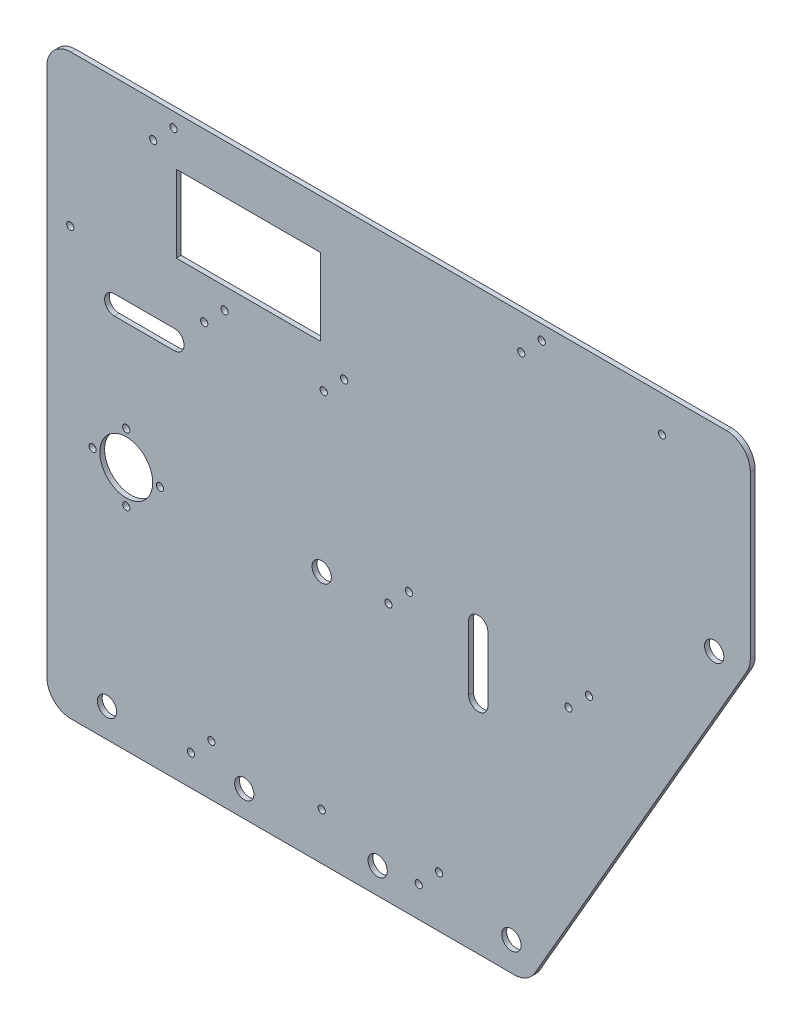
SolidWorks part; units mm, degrees
ref_plane "Front Plane" through (0, 0, 0) normal (0, 0, 1) x (1, 0, 0)
ref_plane "Top Plane" through (0, 0, 0) normal (0, 1, 0) x (1, 0, 0)
ref_plane "Right Plane" through (0, 0, 0) normal (1, 0, 0) x (0, 0, -1)
sketch "Sketch1" plane through (0, 0, 0) normal (0, 0, 1) x (1, 0, 0)
  line L0 (100, 80) -> (192.376, 80)
  line L1 (-100, -80) -> (100, -80)
  line L2 (-100, -80) -> (-100, 80)
  line L3 (-100, 80) -> (100, 80)
  line L4 (100, -80) -> (100, 80)
  line L5 (-100, -80) -> (100, 80) construction
  line L6 (-100, 80) -> (100, -80) construction
  line L7 (192.376, 80) -> (100, -80)
  line L8 (100, 80) -> (100, -80)
  line L10 (-100, 80) -> (192.376, 80)
  line L11 (-100, 80) -> (-100, 110)
  line L12 (-100, 110) -> (192.376, 110)
  line L13 (192.376, 80) -> (192.376, 110)
  point P0 (0, 0)
  dimension "D1" = 160
  dimension "D2" = 200
  dimension "D3" = 30
  dimension "D4" = 30
extrude "Boss-Extrude1" add sketch "Sketch1" along normal blind 2 contours L1 L4 L3 L2 | L7 L0 L4 | L11 L10 L13 L12 region at (0, 0, 0) region at (130.792, 26.6667, 0)
sketch "Sketch2" plane through (0, 0, 2) normal (0, 0, 1) x (1, 0, 0)
  line L0 (-100, -80) -> (100, -80) construction
  line L1 (192.376, 80) -> (100, -80) construction
  line L2 (79.2904, 11.2418) -> (79.2904, 37.9086) construction
  line L3 (-100, -80) -> (-100, 110) construction
  line L4 (-72, 78) -> (-47, 78) construction
  line L7 (-100, 110) -> (192.376, 110) construction
  line L8 (75.2904, 11.2418) -> (75.2904, 37.9086)
  line L9 (-72, 82) -> (-47, 82)
  line L10 (-72, 74) -> (-47, 74)
  line L11 (-100, -80) -> (-100, 110) construction
  line L12 (83.2904, 11.2418) -> (83.2904, 37.9086)
  circle A0 centre (93.0718, -68) radius 4
  circle A1 centre (177.3649, 78) radius 4
  circle A2 centre (-67, 22) radius 11
  circle A3 centre (-75, -68) radius 4
  circle A4 centre (-53, 22) radius 1.5
  circle A5 centre (-67, 36) radius 1.5
  circle A6 centre (-81, 22) radius 1.5
  circle A7 centre (-67, 8) radius 1.5
  circle A11 centre (54.5495, -67.2426) radius 1.5
  circle A12 centre (63.0348, -58.7574) radius 1.5
  circle A13 centre (14.2259, -60.5) radius 1.5
  circle A14 centre (-40.1271, -67.2426) radius 1.5
  circle A15 centre (-31.6419, -58.7574) radius 1.5
  circle A16 centre (-90.2956, 97.2169) radius 1.5
  circle A17 centre (-34.6051, 90.4743) radius 1.5
  circle A18 centre (-26.1198, 98.9596) radius 1.5
  circle A19 centre (15.0782, 90.4743) radius 1.5
  circle A20 centre (23.5635, 98.9596) radius 1.5
  circle A21 centre (41.9695, 27.4743) radius 1.5
  circle A22 centre (50.4548, 35.9596) radius 1.5
  circle A23 centre (-39.813, 27.4743) radius 1.5 construction
  circle A24 centre (-31.3277, 35.9596) radius 1.5 construction
  circle A25 centre (116.8113, 27.4743) radius 1.5
  circle A26 centre (125.2966, 35.9596) radius 1.5
  circle A27 centre (79.2904, 25) radius 4 construction
  circle A28 centre (14.2259, 25) radius 4
  arc A29 (-72, 82) -> (-72, 74) centre (-72, 78) ccw
  arc A30 (-47, 74) -> (-47, 82) centre (-47, 78) ccw
  circle A31 centre (155.6518, 145.1456) radius 1.5
  arc A32 (75.2904, 11.2418) -> (83.2904, 11.2418) centre (79.2904, 11.2418) ccw
  arc A33 (83.2904, 37.9086) -> (75.2904, 37.9086) centre (79.2904, 37.9086) ccw
  circle A34 centre (-55.8147, 145.4743) radius 1.5
  circle A35 centre (-47.3294, 153.9596) radius 1.5
  circle A36 centre (97.1924, 145.4743) radius 1.5
  circle A37 centre (105.6777, 153.9596) radius 1.5
  circle A38 centre (-17.9479, -69.1174) radius 4
  circle A39 centre (37.4944, -69.1174) radius 4
  point P26 (-59.5, 78)
  point P87 (79.2904, 24.5752)
  dimension "D3" = 8
  dimension "D4" = 8
  dimension "D9" = 22
  dimension "D10" = 8
  dimension "D12" = 3
  dimension "D13" = 3
  dimension "D14" = 3
  dimension "D15" = 3
  dimension "D16" = 14
  dimension "D20" = 8
  dimension "D22" = 4
  dimension "D25" = 3
  dimension "D26" = 3
  dimension "D29" = 8
  dimension "D28" = 3
  dimension "D31" = 8
  dimension "D32" = 8
  dimension "D1" = 12
  dimension "D2" = 12
  dimension "D5" = 32
  dimension "D6" = 12
  dimension "D7" = 88
  dimension "D8" = 33
  dimension "D11" = 12
  dimension "D17" = 14
  dimension "D18" = 14
  dimension "D19" = 14
  dimension "D21" = 85
  dimension "D23" = 28
  dimension "D24" = 25
  dimension "D27" = 25
  dimension "D30" = 8
extrude "Cut-Extrude1" cut sketch "Sketch2" against normal blind 3
sketch "Sketch4" plane through (0, 0, 2) normal (0, 0, 1) x (1, 0, 0)
  line L0 (192.376, 80) -> (192.376, 110) construction
  line L1 (-100, 110) -> (192.376, 110)
  line L2 (-100, 110) -> (-100, 160)
  line L3 (-100, 160) -> (192.376, 160)
  line L4 (192.376, 110) -> (192.376, 160)
  dimension "D1" = 50
extrude "Boss-Extrude2" add sketch "Sketch4" against normal blind 2
fillet "Fillet1" radius 10 5 edges at (192.376, 160, 1) (192.376, 80, 1) (100, -80, 1) (-100, -80, 1) (-100, 160, 1)
sketch "Sketch5" plane through (0, 0, 2) normal (0, 0, 1) x (1, 0, 0)
  line L1 (-46.1781, 107.7169) -> (13.8219, 107.7169)
  line L2 (-46.1781, 107.7169) -> (-46.1781, 139.7169)
  line L3 (-46.1781, 139.7169) -> (13.8219, 139.7169)
  line L4 (13.8219, 107.7169) -> (13.8219, 139.7169)
  circle A2 centre (-55.8147, 145.4743) radius 1.5
  circle A3 centre (-47.3294, 153.9596) radius 1.5
  circle A4 centre (97.1924, 145.4743) radius 1.5
  circle A5 centre (105.6777, 153.9596) radius 1.5
  circle A6 centre (155.6518, 145.1456) radius 1.5
  dimension "D1" = 3
extrude "Cut-Extrude2" cut sketch "Sketch5" against normal blind 11
